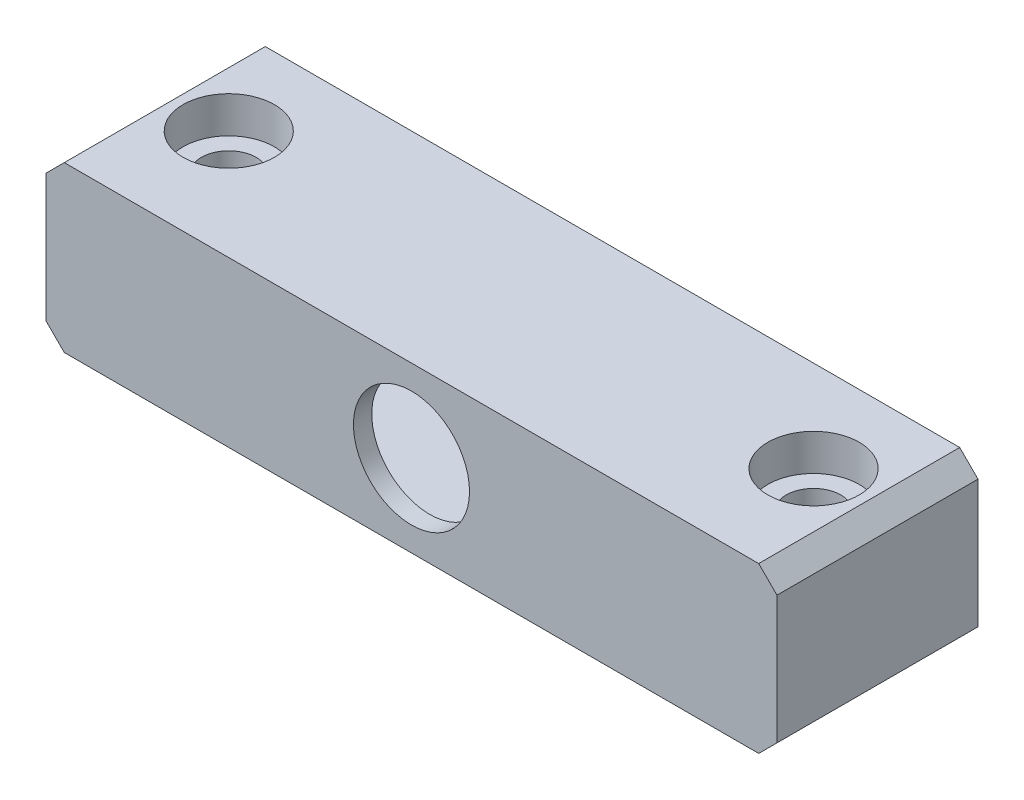
SolidWorks part; units mm, degrees
ref_plane "Front Plane" through (0, 0, 0) normal (0, 0, 1) x (1, 0, 0)
ref_plane "Top Plane" through (0, 0, 0) normal (0, 1, 0) x (1, 0, 0)
ref_plane "Right Plane" through (0, 0, 0) normal (1, 0, 0) x (0, 0, -1)
sketch "Sketch2" plane through (0, 0, 0) normal (0, 0, 1) x (1, 0, 0)
  line L0 (-10, 4.5) -> (10, 4.5)
  line L1 (10, -4.5) -> (-10, -4.5)
  line L2 (-10, 3.5) -> (10, 3.5)
  line L3 (10, -3.5) -> (-10, -3.5)
  line L4 (-10, 4.5) -> (-20, 4.5)
  line L5 (-20, 4.5) -> (-20, -4.5)
  line L6 (-20, -4.5) -> (-10, -4.5)
  line L7 (10, -4.5) -> (20, -4.5)
  line L8 (20, -4.5) -> (20, 4.5)
  line L9 (20, 4.5) -> (10, 4.5)
  arc A2 (10, 3.5) -> (10, -3.5) centre (10, 0) cw
  arc A3 (-10, -3.5) -> (-10, 3.5) centre (-10, 0) cw
  arc A4 (-10, -4.5) -> (-10, 4.5) centre (-10, 0) cw construction
  arc A5 (10, 4.5) -> (10, -4.5) centre (10, 0) cw construction
  point P6 (0, 4.5)
  point P7 (0, -4.5)
  point P15 (0, 0)
  point P20 (0, 3.5)
  point P21 (0, 0)
  dimension "D2" = 3.5
  dimension "D1" = 20
  dimension "D4" = 10
  dimension "D3" = 1
extrude "Boss-Extrude1" add sketch "Sketch2" along normal mid plane 10
extrude "Boss-Extrude2" add sketch "Sketch2<2>" along normal blind 1 from offset 5 contours A3 L3 A2 L2 | L1 L0 L3 A3 L2 A2 region at (0, 4.09, 0) region at (0, 0, 0)
sketch "Sketch2<2>" plane through (0, 0, 0) normal (0, 0, 1) x (1, 0, 0) same geometry as "Sketch2"
sketch "Sketch3" plane through (0, 0, 6) normal (0, 0, 1) x (1, 0, 0)
  circle A0 centre (0, 0) radius 3.175
  dimension "D1" = 6.35
extrude "Cut-Extrude1" cut sketch "Sketch3" against normal up to next contours A0
sketch "Sketch7" plane through (0, 4.5, 0) normal (0, 1, 0) x (1, 0, 0)
  circle A0 centre (-16, 0) radius 2.5
  circle A1 centre (16, 0) radius 2.5
  circle A2 centre (-16, 0) radius 1.5
  circle A3 centre (16, 0) radius 1.5
  dimension "D1" = 5
  dimension "D2" = 16
  dimension "D4" = 3
  dimension "D3" = 32
extrude "Cut-Extrude2" cut sketch "Sketch7" against normal blind 2 contours A1 | A3 | A2 | A0 A2 | A0 region at (-18.4293, 4.5, 0) region at (13.5707, 4.5, 0) region at (-16, 4.5, 0) region at (16, 4.5, 0)
extrude "Cut-Extrude3" cut sketch "Sketch7<3>" against normal through all contours A2 | A3 region at (-16, 4.5, 0) region at (16, 4.5, 0)
sketch "Sketch7<3>" plane through (0, 4.5, 0) normal (0, 1, 0) x (1, 0, 0) same geometry as "Sketch7"
chamfer "Chamfer1" distance 1 angle 45 4 edges at (-20, -4.5, 0.5) (20, -4.5, 0.5) (20, 4.5, 0.5) (-20, 4.5, 0.5)
